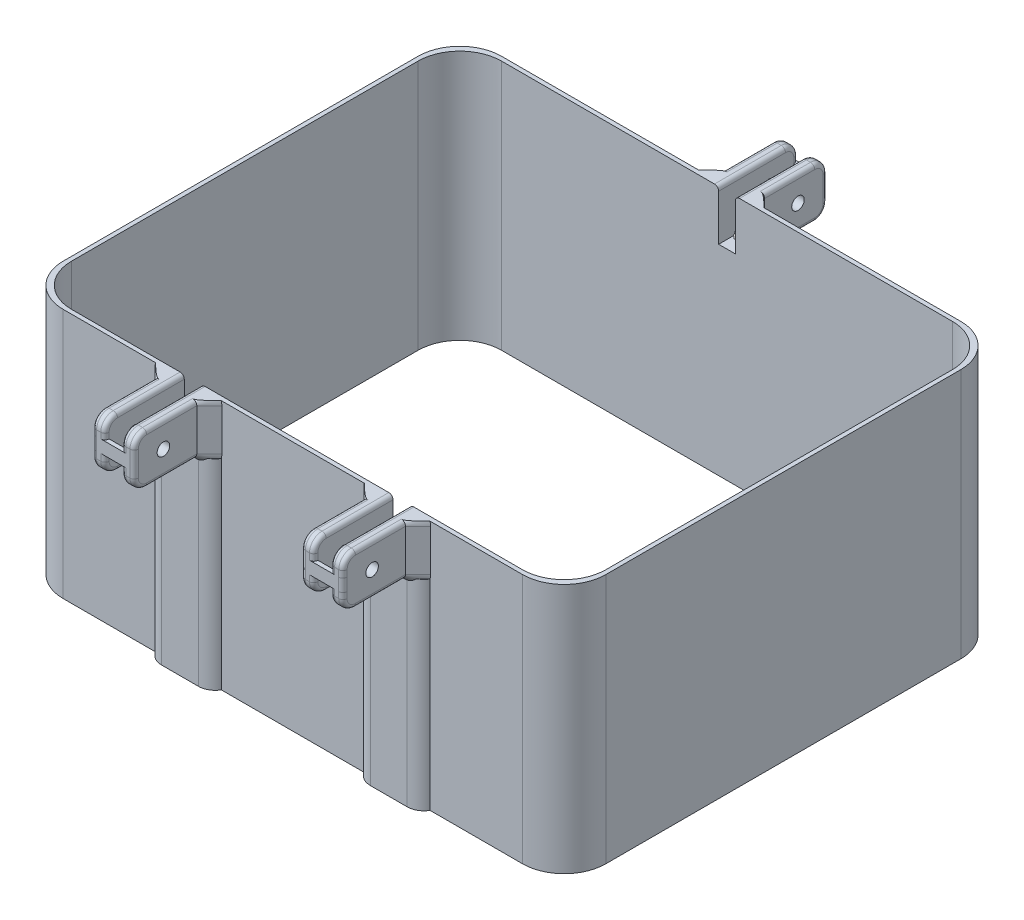
SolidWorks part; units mm, degrees
ref_plane "前视基准面" through (0, 0, 0) normal (0, 0, 1) x (1, 0, 0)
ref_plane "上视基准面" through (0, 0, 0) normal (0, 1, 0) x (1, 0, 0)
ref_plane "右视基准面" through (0, 0, 0) normal (1, 0, 0) x (0, 0, -1)
sketch "草图1" plane through (0, 0, 0) normal (0, 1, 0) x (1, 0, 0)
  line L1 (-47.3679, 69.5108) -> (62.6321, 69.5108)
  line L2 (-57.3679, 59.5108) -> (-57.3679, -25.4892)
  line L3 (-47.3679, -35.4892) -> (62.6321, -35.4892)
  line L4 (72.6321, 59.5108) -> (72.6321, -25.4892)
  line L5 (-46.3679, 68.5108) -> (61.6321, 68.5108)
  line L6 (-56.3679, 58.5108) -> (-56.3679, -24.4892)
  line L7 (-46.3679, -34.4892) -> (61.6321, -34.4892)
  line L8 (71.6321, 58.5108) -> (71.6321, -24.4892)
  arc A0 (-57.3679, -25.4892) -> (-47.3679, -35.4892) centre (-47.3679, -25.4892) ccw
  arc A1 (-56.3679, -24.4892) -> (-46.3679, -34.4892) centre (-46.3679, -24.4892) ccw
  arc A2 (62.6321, -35.4892) -> (72.6321, -25.4892) centre (62.6321, -25.4892) ccw
  arc A3 (61.6321, -34.4892) -> (71.6321, -24.4892) centre (61.6321, -24.4892) ccw
  arc A4 (61.6321, 68.5108) -> (71.6321, 58.5108) centre (61.6321, 58.5108) cw
  arc A5 (62.6321, 69.5108) -> (72.6321, 59.5108) centre (62.6321, 59.5108) cw
  arc A6 (-47.3679, 69.5108) -> (-57.3679, 59.5108) centre (-47.3679, 59.5108) ccw
  arc A7 (-46.3679, 68.5108) -> (-56.3679, 58.5108) centre (-46.3679, 58.5108) ccw
  dimension "D7" = 10
  dimension "D1" = 130
  dimension "D2" = 105
  dimension "D3" = 1
  dimension "D4" = 1
  dimension "D5" = 1
  dimension "D6" = 1
extrude "凸台-拉伸2" add sketch "草图1" along normal blind 60
ref_plane "基准面1" through (37.6321, 0, 0) normal (1, 0, 0) x (0, 0, -1)
sketch "草图2" plane through (37.6321, 0, 0) normal (1, 0, 0) x (0, 0, -1)
  line L1 (-35.4892, 60) -> (-50.4892, 60)
  line L2 (-35.4892, 60) -> (-35.4892, 48)
  line L3 (-35.4892, 48) -> (-50.4892, 48)
  line L4 (-53.4892, 57) -> (-53.4892, 51)
  arc A0 (-50.4892, 48) -> (-53.4892, 51) centre (-50.4892, 51) cw
  arc A1 (-50.4892, 60) -> (-53.4892, 57) centre (-50.4892, 57) ccw
  dimension "D3" = 3
  dimension "D1" = 18
  dimension "D2" = 12
extrude "凸台-拉伸4" add sketch "草图2" against normal blind 60
sketch "草图3" plane through (37.6321, 0, 0) normal (1, 0, 0) x (0, 0, -1)
  line L0 (-46.4892, 87.9975) -> (-46.4892, 3.822) construction
  line L1 (-53.4892, 57) -> (-53.4892, 51) construction
  line L2 (-71.8345, 54) -> (5.3565, 54) construction
  circle A0 centre (-46.4892, 54) radius 1.5
  dimension "D2" = 3
  dimension "D1" = 7
extrude "切除-拉伸1" cut sketch "草图3" against normal blind 60
sketch "草图4" plane through (0, 60, 0) normal (0, 1, 0) x (1, 0, 0)
  line L2 (-12.3679, -35.4892) -> (-12.3679, -70.1936)
  line L3 (-12.3679, -70.1936) -> (27.6321, -70.1936)
  line L4 (27.6321, -35.4892) -> (27.6321, -70.1936)
  line L5 (-22.3679, -35.4892) -> (-22.3679, -50.4892) construction
  line L6 (37.6321, -58.5391) -> (37.6321, 58.5391) construction
  line L7 (27.6321, -35.4892) -> (-12.3679, -35.4892)
  dimension "D1" = 10
  dimension "D2" = 10
extrude "切除-拉伸3" cut sketch "草图4" against normal blind 60
sketch "草图5" plane through (0, 60, 0) normal (0, 1, 0) x (1, 0, 0)
  line L0 (-46.3679, -34.4892) -> (61.6321, -34.4892) construction
  line L1 (-19.3679, -34.4892) -> (-15.3679, -34.4892)
  line L2 (-19.3679, -34.4892) -> (-19.3679, -53.4892)
  line L3 (-19.3679, -53.4892) -> (-15.3679, -53.4892)
  line L4 (-15.3679, -34.4892) -> (-15.3679, -53.4892)
  line L5 (-22.3679, -53.4892) -> (-12.3679, -53.4892) construction
  line L6 (-22.3679, -35.4892) -> (-22.3679, -50.4892) construction
  line L7 (-12.3679, -35.4892) -> (-12.3679, -50.4892) construction
  line L8 (27.6321, -53.4892) -> (37.6321, -53.4892) construction
  line L9 (30.6321, -34.4892) -> (34.6321, -34.4892)
  line L10 (30.6321, -34.4892) -> (30.6321, -53.4892)
  line L11 (30.6321, -53.4892) -> (34.6321, -53.4892)
  line L12 (34.6321, -34.4892) -> (34.6321, -53.4892)
  line L13 (27.6321, -50.4892) -> (27.6321, -35.4892) construction
  line L14 (37.6321, -58.5391) -> (37.6321, 58.5391) construction
  dimension "D1" = 3
  dimension "D2" = 3
  dimension "D3" = 3
  dimension "D4" = 3
extrude "切除-拉伸4" cut sketch "草图5" against normal blind 12
fillet "圆角1" radius 1 5 edges at (-22.3679, 48, 42.9892) (-22.3679, 48.8787, 52.6106) (-22.3679, 54, 53.4892) (-22.3679, 59.1213, 52.6106) (-22.3679, 60, 42.9892)
fillet "圆角2" radius 1 5 edges at (-19.3679, 48, 42.9892) (-19.3679, 48.8787, 52.6106) (-19.3679, 54, 53.4892) (-19.3679, 59.1213, 52.6106) (-19.3679, 60, 42.4892)
fillet "圆角3" radius 1 5 edges at (-15.3679, 48, 42.9892) (-15.3679, 48.8787, 52.6106) (-15.3679, 54, 53.4892) (-15.3679, 59.1213, 52.6106) (-15.3679, 60, 42.4892)
fillet "圆角4" radius 1 5 edges at (-12.3679, 48, 42.9892) (-12.3679, 48.8787, 52.6106) (-12.3679, 54, 53.4892) (-12.3679, 59.1213, 52.6106) (-12.3679, 60, 42.9892)
fillet "圆角5" radius 1 5 edges at (27.6321, 48, 42.9892) (27.6321, 48.8787, 52.6106) (27.6321, 54, 53.4892) (27.6321, 59.1213, 52.6106) (27.6321, 60, 42.9892)
fillet "圆角6" radius 1 5 edges at (34.6321, 48, 42.9892) (34.6321, 48.8787, 52.6106) (34.6321, 54, 53.4892) (34.6321, 60, 42.4892) (34.6321, 59.1213, 52.6106)
fillet "圆角7" radius 1 5 edges at (30.6321, 48, 42.9892) (30.6321, 48.8787, 52.6106) (30.6321, 54, 53.4892) (30.6321, 59.1213, 52.6106) (30.6321, 60, 42.4892)
fillet "圆角8" radius 1 5 edges at (37.6321, 48, 42.9892) (37.6321, 48.8787, 52.6106) (37.6321, 54, 53.4892) (37.6321, 59.1213, 52.6106) (37.6321, 60, 42.9892)
ref_plane "基准面2" through (7.6321, 0, 0) normal (1, 0, 0) x (0, 0, -1)
sketch "草图6" plane through (7.6321, 0, 0) normal (1, 0, 0) x (0, 0, -1)
  line L0 (95.5673, 54) -> (39.7155, 54) construction
  line L1 (69.5108, 60) -> (84.5108, 60)
  line L2 (69.5108, 60) -> (69.5108, 48)
  line L3 (69.5108, 48) -> (84.5108, 48)
  line L4 (87.5108, 57) -> (87.5108, 51)
  line L5 (80.5108, 83.314) -> (80.5108, -0.4637) construction
  arc A0 (84.5108, 48) -> (87.5108, 51) centre (84.5108, 51) ccw
  arc A1 (84.5108, 60) -> (87.5108, 57) centre (84.5108, 57) cw
  circle A2 centre (80.5108, 54) radius 1.5
  dimension "D3" = 3
  dimension "D5" = 3
  dimension "D1" = 18
  dimension "D2" = 12
  dimension "D4" = 7
extrude "凸台-拉伸5" add sketch "草图6" against normal mid plane 10 contours L2 L1 A1 L4 A0 L3 | A2
sketch "草图7" plane through (0, 60, 0) normal (0, 1, 0) x (1, 0, 0)
  line L0 (61.6321, 68.5108) -> (-46.3679, 68.5108) construction
  line L1 (5.6321, 68.5108) -> (9.6321, 68.5108)
  line L2 (5.6321, 68.5108) -> (5.6321, 95.6595)
  line L3 (5.6321, 95.6595) -> (9.6321, 95.6595)
  line L4 (9.6321, 68.5108) -> (9.6321, 95.6595)
  line L5 (2.6321, 69.5108) -> (2.6321, 84.5108) construction
  line L6 (12.6321, 69.5108) -> (12.6321, 84.5108) construction
  dimension "D1" = 3
  dimension "D2" = 3
extrude "切除-拉伸5" cut sketch "草图7" against normal blind 12
fillet "圆角9" radius 1 5 edges at (12.6321, 48, -77.0108) (12.6321, 48.8787, -86.6321) (12.6321, 54, -87.5108) (12.6321, 59.1213, -86.6321) (12.6321, 60, -77.0108)
fillet "圆角10" radius 1 5 edges at (2.6321, 48, -77.0108) (2.6321, 48.8787, -86.6321) (2.6321, 54, -87.5108) (2.6321, 59.1213, -86.6321) (2.6321, 60, -77.0108)
fillet "圆角11" radius 1 5 edges at (9.6321, 48, -77.0108) (9.6321, 48.8787, -86.6321) (9.6321, 54, -87.5108) (9.6321, 59.1213, -86.6321) (9.6321, 60, -76.5108)
fillet "圆角12" radius 1 5 edges at (5.6321, 60, -76.5108) (5.6321, 59.1213, -86.6321) (5.6321, 54, -87.5108) (5.6321, 48, -77.0108) (5.6321, 48.8787, -86.6321)
sketch "草图8" plane through (37.6321, 0, 0) normal (1, 0, 0) x (0, 0, -1)
  line L0 (-52.4892, 57) -> (-52.4892, 51) construction
  line L1 (-52.4892, 55.4497) -> (-53.4892, 55.4497)
  line L2 (-52.4892, 55.4497) -> (-52.4892, 52.4497)
  line L3 (-52.4892, 52.4497) -> (-53.4892, 52.4497)
  line L4 (-53.4892, 55.4497) -> (-53.4892, 52.4497)
  line L5 (-53.4892, 51) -> (-53.4892, 57) construction
  line L6 (-52.4892, 57) -> (-53.4892, 57) construction
  point P10 (-52.9892, 57)
  dimension "D1" = 3
  dimension "D2" = 1.5503
extrude "凸台-拉伸6" add sketch "草图8" against normal up to vertex
fillet "圆角13" radius 1 1 edges at (37.6321, 53.9497, 53.4892)
sketch "草图9" plane through (-22.3679, 0, 0) normal (-1, 0, 0) x (0, 0, 1)
  line L0 (52.4892, 51) -> (52.4892, 57) construction
  line L1 (52.4892, 55.6219) -> (53.4892, 55.6219)
  line L2 (52.4892, 55.6219) -> (52.4892, 52.6219)
  line L3 (52.4892, 52.6219) -> (53.4892, 52.6219)
  line L4 (53.4892, 55.6219) -> (53.4892, 52.6219)
  line L5 (53.4892, 57) -> (53.4892, 51) construction
  dimension "D1" = 3
extrude "凸台-拉伸7" add sketch "草图9" against normal up to vertex
fillet "圆角14" radius 1 1 edges at (-22.3679, 54.1219, 53.4892)
sketch "草图10" plane through (2.6321, 0, 0) normal (-1, 0, 0) x (0, 0, 1)
  line L0 (-87.5108, 51) -> (-87.5108, 57) construction
  line L1 (-87.5108, 55.6731) -> (-86.5108, 55.6731)
  line L2 (-87.5108, 55.6731) -> (-87.5108, 52.6731)
  line L3 (-87.5108, 52.6731) -> (-86.5108, 52.6731)
  line L4 (-86.5108, 55.6731) -> (-86.5108, 52.6731)
  line L5 (-86.5108, 57) -> (-86.5108, 51) construction
  dimension "D1" = 3
extrude "凸台-拉伸8" add sketch "草图10" against normal up to vertex
fillet "圆角15" radius 1 1 edges at (2.6321, 54.1731, -87.5108)
chamfer "倒角1" distance 3 angle 45 5 edges at (30.3392, 48.2929, 35.4892) (29.1321, 48, 35.4892) (27.925, 48.2929, 35.4892) (27.925, 59.7071, 35.4892) (27.6321, 54, 35.4892)
chamfer "倒角2" distance 3 angle 45 5 edges at (34.925, 48.2929, 35.4892) (36.1321, 48, 35.4892) (37.3392, 48.2929, 35.4892) (37.3392, 59.7071, 35.4892) (37.6321, 54, 35.4892)
chamfer "倒角3" distance 3 angle 45 5 edges at (-15.075, 48.2929, 35.4892) (-13.8679, 48, 35.4892) (-12.6608, 48.2929, 35.4892) (-12.6608, 59.7071, 35.4892) (-12.3679, 54, 35.4892)
chamfer "倒角4" distance 3 angle 45 5 edges at (-19.6608, 48.2929, 35.4892) (-20.8679, 48, 35.4892) (-22.075, 48.2929, 35.4892) (-22.075, 59.7071, 35.4892) (-22.3679, 54, 35.4892)
chamfer "倒角5" distance 3 angle 45 5 edges at (9.925, 48.2929, -69.5108) (11.1321, 48, -69.5108) (12.3392, 59.7071, -69.5108) (12.3392, 48.2929, -69.5108) (12.6321, 54, -69.5108)
chamfer "倒角6" distance 3 angle 45 5 edges at (5.3392, 48.2929, -69.5108) (4.1321, 48, -69.5108) (2.925, 59.7071, -69.5108) (2.925, 48.2929, -69.5108) (2.6321, 54, -69.5108)
sketch "草图12" plane through (0, 0, 35.4892) normal (0, 0, 1) x (1, 0, 0)
  line L0 (-47.3679, 0) -> (62.6321, 0) construction
  line L1 (29.6321, 48) -> (35.6321, 48)
  line L3 (29.6321, 0) -> (35.6321, 0)
  line L5 (29.6321, 48) -> (24.7591, 48)
  line L6 (24.7591, 48) -> (24.7591, 0)
  line L7 (24.7591, 0) -> (29.6321, 0)
  line L8 (35.6321, 48) -> (40.5051, 48)
  line L9 (40.5051, 48) -> (40.5051, 0)
  line L10 (40.5051, 0) -> (35.6321, 0)
  arc A0 (24.6321, 49) -> (28.6321, 45) centre (28.6321, 49) ccw construction
  arc A1 (36.6321, 45) -> (40.6321, 49) centre (36.6321, 49) ccw construction
sketch "草图13" plane through (0, 0, 35.4892) normal (0, 0, 1) x (1, 0, 0)
  line L0 (-47.3679, 0) -> (62.6321, 0) construction
  line L1 (-20.3679, 48) -> (-14.3679, 48)
  line L3 (-20.3679, 0) -> (-14.3679, 0)
  line L5 (-20.3679, 48) -> (-25.2409, 48)
  line L6 (-25.2409, 48) -> (-25.2409, 0)
  line L7 (-25.2409, 0) -> (-20.3679, 0)
  line L8 (-14.3679, 48) -> (-9.4949, 48)
  line L9 (-9.4949, 48) -> (-9.4949, 0)
  line L10 (-9.4949, 0) -> (-14.3679, 0)
  arc A0 (-25.3679, 49) -> (-21.3679, 45) centre (-21.3679, 49) ccw construction
  arc A1 (-13.3679, 45) -> (-9.3679, 49) centre (-13.3679, 49) ccw construction
sketch "草图14" plane through (0, 0, -69.5108) normal (0, 0, -1) x (-1, 0, 0)
  line L0 (-62.6321, 0) -> (47.3679, 0) construction
  line L1 (-10.6321, 48) -> (-4.6321, 48)
  line L3 (-10.6321, 0) -> (-4.6321, 0)
  line L5 (-4.6321, 48) -> (0.2409, 48)
  line L6 (0.2409, 48) -> (0.2409, 0)
  line L7 (0.2409, 0) -> (-4.6321, 0)
  line L8 (-10.6321, 48) -> (-15.5051, 48)
  line L9 (-15.5051, 48) -> (-15.5051, 0)
  line L10 (-15.5051, 0) -> (-10.6321, 0)
  arc A0 (-3.6321, 45) -> (0.3679, 49) centre (-3.6321, 49) ccw construction
  arc A1 (-15.6321, 49) -> (-11.6321, 45) centre (-11.6321, 49) ccw construction
extrude "凸台-拉伸12" add sketch "草图14" along normal blind 2
fillet "圆角24" radius 4 1 edges at (15.5051, 24, -71.5108)
fillet "圆角25" radius 4 1 edges at (-0.2409, 24, -71.5108)
extrude "凸台-拉伸13" add sketch "草图13" along normal blind 2
fillet "圆角26" radius 4 1 edges at (-25.2409, 24, 37.4892)
fillet "圆角27" radius 4 1 edges at (-9.4949, 24, 37.4892)
extrude "凸台-拉伸14" add sketch "草图12" along normal blind 2
fillet "圆角28" radius 4 2 edges at (40.5051, 24, 37.4892) (24.7591, 24, 37.4892)
